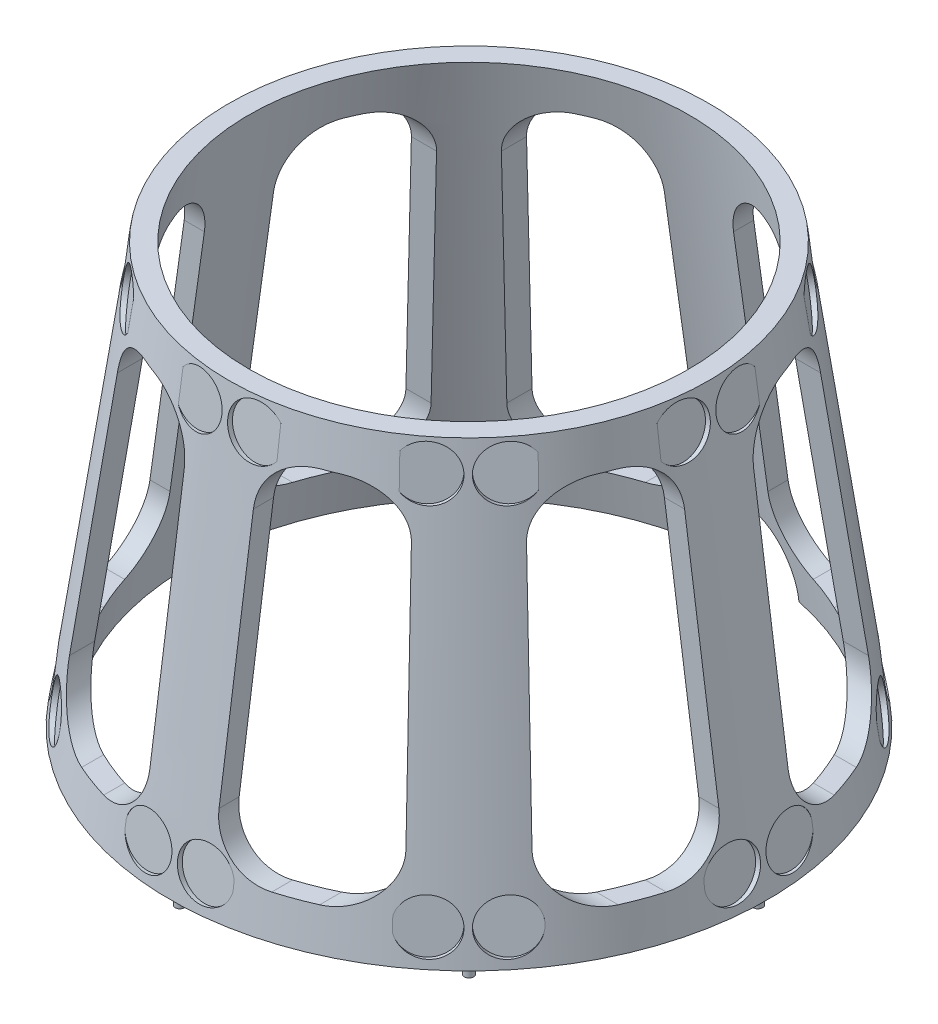
SolidWorks part; units mm, degrees
ref_plane "Ebene vorne" through (0, 0, 0) normal (0, 0, 1) x (1, 0, 0)
ref_plane "Ebene oben" through (0, 0, 0) normal (0, 1, 0) x (1, 0, 0)
ref_plane "Ebene rechts" through (0, 0, 0) normal (1, 0, 0) x (0, 0, -1)
sketch "Skizze1" plane through (0, 0, 0) normal (1, 0, 0) x (0, 0, -1)
  line L0 (56.5, 0) -> (44.554, 85)
  line L2 (55, 0) -> (-55, 0) construction
  line L3 (44.554, 85) -> (48.5933, 85)
  line L4 (48.5933, 85) -> (60.5393, 0)
  line L5 (60.5393, 0) -> (56.5, 0)
  line L6 (0, 50.9975) -> (0, -22.934) construction
  line L7 (0, 55) -> (0, -55) construction
  dimension "D1" = 56.5
  dimension "D2" = 98
  dimension "D3" = 85
  dimension "D4" = 4
revolve "Rotation1" add sketch "Skizze1" angle 360 about L6
sketch "Skizze2" plane through (0, 0, 0) normal (0, -1, 0) x (1, 0, 0)
  line L0 (0, 58.5) -> (0, -58.5) construction
  line L1 (64.5273, 1.9503) -> (58.5, 0) construction
  line L2 (58.5, 0) -> (-58.5, 0) construction
  line L3 (0, 0) -> (-41.3657, 41.3657) construction
  line L4 (0, 0) -> (41.3657, -41.3657) construction
  circle A1 centre (0, -58.5) radius 0.95
  circle A2 centre (-41.3657, -41.3657) radius 0.95
  circle A3 centre (-58.5, 0) radius 0.95
  circle A4 centre (-41.3657, 41.3657) radius 0.95
  circle A5 centre (0, 58.5) radius 0.95
  circle A6 centre (41.3657, 41.3657) radius 0.95
  circle A7 centre (58.5, 0) radius 0.95
  circle A8 centre (41.3657, -41.3657) radius 0.95
  point P27 (0, 0)
  dimension "D1" = 1.9
  dimension "D2" = 8
extrude "Aufsatz-Linear austragen1" add sketch "Skizze2" along normal blind 2
sketch "Skizze3" plane through (0, 0, 0) normal (1, 0, 0) x (0, 0, -1)
  line L0 (-7, 67) -> (-7, 18)
  line L1 (-17, 8) -> (-24.0869, 8)
  line L2 (-34.0489, 18.8716) -> (-29.7619, 67.8716)
  line L3 (-19.8, 77) -> (-17, 77)
  line L4 (44.554, 85) -> (-44.554, 85) construction
  line L5 (0, 47.85) -> (0, -47.85) construction
  line L10 (19.8, 77) -> (17, 77)
  line L11 (34.0489, 18.8716) -> (29.7619, 67.8716)
  line L12 (17, 8) -> (24.0869, 8)
  line L13 (7, 67) -> (7, 18)
  line L14 (0, 0) -> (-53.033, 0) construction
  arc A0 (-24.0869, 8) -> (-34.0489, 18.8716) centre (-24.0869, 18) cw
  arc A1 (-17, 8) -> (-7, 18) centre (-17, 18) ccw
  arc A2 (-17, 77) -> (-7, 67) centre (-17, 67) cw
  arc A3 (-19.8, 77) -> (-29.7619, 67.8716) centre (-19.8, 67) ccw
  arc A4 (19.8, 77) -> (29.7619, 67.8716) centre (19.8, 67) cw
  arc A5 (17, 77) -> (7, 67) centre (17, 67) ccw
  arc A6 (17, 8) -> (7, 18) centre (17, 18) cw
  arc A7 (24.0869, 8) -> (34.0489, 18.8716) centre (24.0869, 18) ccw
  point P12 (-35, 8)
  point P15 (-7, 8)
  point P18 (-7, 77)
  point P21 (-28.9633, 77)
  point P30 (28.9633, 77)
  point P31 (7, 77)
  point P32 (7, 8)
  point P33 (35, 8)
  point P34 (-18.4, 77)
  dimension "D4" = 10
  dimension "D1" = 85
  dimension "D2" = 7
  dimension "D3" = 28
  dimension "D5" = 8
  dimension "D6" = 8
extrude "Schnitt-Linear austragen1" cut sketch "Skizze3" against normal through all and the other way through all
sketch "Skizze4" plane through (0, 0, 0) normal (0, 0, 1) x (1, 0, 0)
  line L0 (-7, 67) -> (-7, 18)
  line L1 (-17, 8) -> (-24.0869, 8)
  line L2 (-34.0489, 18.8716) -> (-29.7619, 67.8716)
  line L3 (-19.8, 77) -> (-17, 77)
  line L4 (0, -47.85) -> (0, 47.85) construction
  line L5 (17, 8) -> (24.0869, 8)
  line L10 (34.0489, 18.8716) -> (29.7619, 67.8716)
  line L11 (19.8, 77) -> (17, 77)
  line L12 (7, 67) -> (7, 18)
  line L13 (44.554, 85) -> (-44.554, 85) construction
  line L15 (0, 0) -> (-53.033, 0) construction
  arc A0 (17, 8) -> (7, 18) centre (17, 18) cw
  arc A1 (7, 67) -> (17, 77) centre (17, 67) cw
  arc A2 (29.7619, 67.8716) -> (19.8, 77) centre (19.8, 67) ccw
  arc A3 (34.0489, 18.8716) -> (24.0869, 8) centre (24.0869, 18) cw
  arc A4 (-24.0869, 8) -> (-34.0489, 18.8716) centre (-24.0869, 18) cw
  arc A5 (-17, 8) -> (-7, 18) centre (-17, 18) ccw
  arc A6 (-17, 77) -> (-7, 67) centre (-17, 67) cw
  arc A7 (-19.8, 77) -> (-29.7619, 67.8716) centre (-19.8, 67) ccw
  point P12 (7, 8)
  point P15 (7, 77)
  point P18 (28.9633, 77)
  point P21 (35, 8)
  point P24 (-35, 8)
  point P27 (-7, 8)
  point P30 (-7, 77)
  point P33 (-28.9633, 77)
  dimension "D2" = 10
  dimension "D1" = 85
  dimension "D3" = 28
  dimension "D4" = 7
  dimension "D5" = 8
  dimension "D6" = 8
extrude "Schnitt-Linear austragen2" cut sketch "Skizze4" against normal through all and the other way through all
ref_plane "Ebene1" through (-59.3667, 8.3434, 0) normal (-0.9903, 0.1392, 0) x (0, 0, 1)
sketch "Skizze6" plane through (-59.3667, 8.3434, 0) normal (-0.9903, 0.1392, 0) x (0, 0, 1)
  line L0 (0, -47.85) -> (0, 47.85) construction
  line L1 (0, 77.4099) -> (0, -8.4254) construction
  line L2 (0, 34.4922) -> (5.8, 34.4922) construction
  line L3 (93.5748, 3.1727) -> (93.1179, 3.2641) construction
  circle A0 centre (5.8, 71.4922) radius 5.2
  circle A1 centre (5.8, -1.5078) radius 5.2
  circle A2 centre (-5.8, 71.4922) radius 5.2
  circle A3 centre (-5.8, -1.5078) radius 5.2
  ellipse E0 centre (0, 84.1728) end of major axis (48.5933, 84.1728) minor radius 6.7629 construction
  ellipse E1 centre (0, 0) end of major axis (60.5393, 0) minor radius 8.4254 construction
  dimension "D2" = 10.4
  dimension "D3" = 10.4
  dimension "D1" = 5.8
  dimension "D4" = 5.8
  dimension "D5" = 73
  dimension "D6" = 37
extrude "Schnitt-Linear austragen3" cut sketch "Skizze6" against normal blind 1
ref_plane "Ebene2" through (0, 8.3434, 59.3667) normal (0, 0.1392, 0.9903) x (1, 0, 0)
ref_plane "Ebene3" through (59.3667, 8.3434, 0) normal (0.9903, 0.1392, 0) x (0, 0, -1)
ref_plane "Ebene4" through (0, 8.3434, -59.3667) normal (0, 0.1392, -0.9903) x (-1, 0, 0)
ref_axis "Achse1" through (0, 89.35, 0) along (0, -1, 0)
ref_plane "Ebene9" through (0, 0, 0) normal (-0.7071, 0, 0.7071) x (0, -1, 0)
ref_plane "Ebene10" through (0, 0, 0) normal (-0.7071, 0, -0.7071) x (0, -1, 0)
ref_plane "Ebene11" through (-41.9786, 8.3434, 41.9786) normal (-0.7002, 0.1392, 0.7002) x (0.6868, -0.1365, 0.7139)
ref_plane "Ebene12" through (41.9786, 8.3434, -41.9786) normal (0.7002, 0.1392, -0.7002) x (-0.6868, -0.1365, -0.7139)
ref_plane "Ebene13" through (41.9786, 8.3434, 41.9786) normal (0.7002, 0.1392, 0.7002) x (0.7139, -0.1365, -0.6868)
ref_plane "Ebene14" through (-41.9786, 8.3434, -41.9786) normal (-0.7002, 0.1392, -0.7002) x (-0.7139, -0.1365, 0.6868)
sketch "Skizze12" plane through (-41.9786, 8.3434, 41.9786) normal (-0.7002, 0.1392, 0.7002) x (0.6868, -0.1365, 0.7139)
  line L0 (-10.7798, 76.6557) -> (1.0521, -8.3602) construction
  line L1 (-4.8639, 34.1478) -> (1.0387, 34.9692) construction
  circle A0 centre (-4.2195, 71.5941) radius 5.2
  circle A1 centre (5.8432, -0.7091) radius 5.2
  circle A2 centre (-5.6461, -2.3081) radius 5.2
  circle A3 centre (-15.7088, 69.9951) radius 5.2
  ellipse E0 centre (-11.6028, 83.3693) end of major axis (36.5267, 90.0676) minor radius 6.7629 construction
  ellipse E1 centre (0, 0) end of major axis (59.9614, 8.345) minor radius 8.4254 construction
  dimension "D1" = 10.4
  dimension "D2" = 10.4
  dimension "D6" = 90
  dimension "D7" = 37
  dimension "D3" = 5.8
  dimension "D4" = 73
  dimension "D5" = 5.8
extrude "Schnitt-Linear austragen7" cut sketch "Skizze12" against normal blind 1
sketch "Skizze14" plane through (0, 8.3434, -59.3667) normal (0, 0.1392, -0.9903) x (-1, 0, 0)
  line L1 (0, 77.4099) -> (0, -8.4254) construction
  line L2 (0, 34.4922) -> (5.8, 34.4922) construction
  line L3 (93.5748, 3.1727) -> (93.1179, 3.2641) construction
  circle A0 centre (5.8, 71.4922) radius 5.2
  circle A2 centre (-5.8, 71.4922) radius 5.2
  dimension "D2" = 10.4
  dimension "D6" = 37
extrude "Schnitt-Linear austragen8" cut sketch "Skizze14" against normal blind 1
sketch "Skizze15" plane through (59.3667, 8.3434, 0) normal (0.9903, 0.1392, 0) x (0, 0, -1)
  line L1 (0, 77.4099) -> (0, -8.4254) construction
  line L2 (0, 34.4922) -> (5.8, 34.4922) construction
  line L3 (93.5748, 3.1727) -> (93.1179, 3.2641) construction
  circle A0 centre (5.8, 71.4922) radius 5.2
  circle A1 centre (5.8, -1.5078) radius 5.2
  circle A2 centre (-5.8, 71.4922) radius 5.2
  circle A3 centre (-5.8, -1.5078) radius 5.2
  dimension "D2" = 10.4
  dimension "D3" = 10.4
  dimension "D5" = 73
  dimension "D6" = 37
extrude "Schnitt-Linear austragen9" cut sketch "Skizze15" against normal blind 1
sketch "Skizze16" plane through (0, 8.3434, 59.3667) normal (0, 0.1392, 0.9903) x (1, 0, 0)
  line L1 (0, 77.4099) -> (0, -8.4254) construction
  line L2 (0, 34.4922) -> (5.8, 34.4922) construction
  line L3 (93.5748, 3.1727) -> (93.1179, 3.2641) construction
  circle A0 centre (5.8, 71.4922) radius 5.2
  circle A1 centre (5.8, -1.5078) radius 5.2
  circle A2 centre (-5.8, 71.4922) radius 5.2
  circle A3 centre (-5.8, -1.5078) radius 5.2
  dimension "D2" = 10.4
  dimension "D3" = 10.4
  dimension "D5" = 73
  dimension "D6" = 37
extrude "Schnitt-Linear austragen10" cut sketch "Skizze16" against normal blind 1
sketch "Skizze17" plane through (41.9786, 8.3434, 41.9786) normal (0.7002, 0.1392, 0.7002) x (0.7139, -0.1365, -0.6868)
  line L0 (-10.7798, 76.6557) -> (1.0521, -8.3602) construction
  line L1 (-4.8639, 34.1478) -> (1.0387, 34.9692) construction
  circle A0 centre (-4.2195, 71.5941) radius 5.2
  circle A1 centre (5.8432, -0.7091) radius 5.2
  circle A2 centre (-5.6461, -2.3081) radius 5.2
  circle A3 centre (-15.7088, 69.9951) radius 5.2
  dimension "D1" = 10.4
  dimension "D2" = 10.4
  dimension "D6" = 90
  dimension "D7" = 37
  dimension "D3" = 5.8
  dimension "D4" = 73
  dimension "D5" = 5.8
extrude "Schnitt-Linear austragen11" cut sketch "Skizze17" against normal blind 1
sketch "Skizze18" plane through (41.9786, 8.3434, -41.9786) normal (0.7002, 0.1392, -0.7002) x (-0.6868, -0.1365, -0.7139)
  line L0 (-10.7798, 76.6557) -> (1.0521, -8.3602) construction
  line L1 (-4.8639, 34.1478) -> (1.0387, 34.9692) construction
  circle A0 centre (-4.2195, 71.5941) radius 5.2
  circle A1 centre (5.8432, -0.7091) radius 5.2
  circle A2 centre (-5.6461, -2.3081) radius 5.2
  circle A3 centre (-15.7088, 69.9951) radius 5.2
  dimension "D1" = 10.4
  dimension "D2" = 10.4
  dimension "D6" = 90
  dimension "D7" = 37
  dimension "D3" = 5.8
  dimension "D4" = 73
  dimension "D5" = 5.8
extrude "Schnitt-Linear austragen12" cut sketch "Skizze18" against normal blind 1
sketch "Skizze19" plane through (-41.9786, 8.3434, -41.9786) normal (-0.7002, 0.1392, -0.7002) x (-0.7139, -0.1365, 0.6868)
  line L0 (-10.7798, 76.6557) -> (1.0521, -8.3602) construction
  line L1 (-4.8639, 34.1478) -> (1.0387, 34.9692) construction
  circle A0 centre (-4.2195, 71.5941) radius 5.2
  circle A1 centre (5.8432, -0.7091) radius 5.2
  circle A2 centre (-5.6461, -2.3081) radius 5.2
  circle A3 centre (-15.7088, 69.9951) radius 5.2
  dimension "D1" = 10.4
  dimension "D2" = 10.4
  dimension "D6" = 90
  dimension "D7" = 37
  dimension "D3" = 5.8
  dimension "D4" = 73
  dimension "D5" = 5.8
extrude "Schnitt-Linear austragen13" cut sketch "Skizze19" against normal blind 1
sketch "Skizze20" plane through (0, 8.3434, -59.3667) normal (0, 0.1392, -0.9903) x (-1, 0, 0)
  circle A0 centre (0, -6.8503) radius 11.5
  dimension "D1" = 23
extrude "Schnitt-Linear austragen15" cut sketch "Skizze20" against normal blind 10
